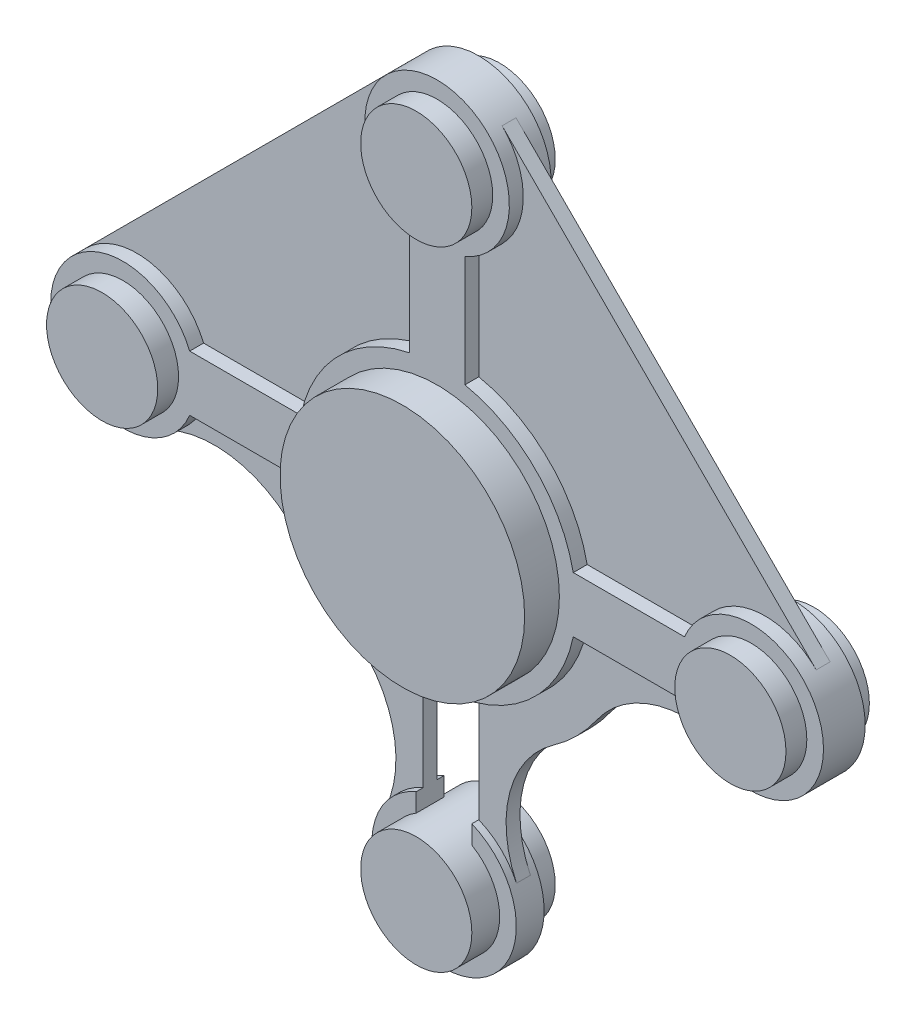
SolidWorks part; units mm, degrees
ref_plane "Front Plane" through (0, 0, 0) normal (0, 0, 1) x (1, 0, 0)
ref_plane "Top Plane" through (0, 0, 0) normal (0, 1, 0) x (1, 0, 0)
ref_plane "Right Plane" through (0, 0, 0) normal (1, 0, 0) x (0, 0, -1)
sketch "Sketch1" plane through (0, 0, 0) normal (0, 0, 1) x (1, 0, 0)
  line L0 (0, 0) -> (50000, 0) construction
  line L1 (0, 0) -> (0, 50000) construction
  line L2 (18.3848, 131.3848) -> (131.3848, 18.3848)
  line L3 (-18.3848, 131.3848) -> (-131.3848, 18.3848)
  line L4 (10, 89) -> (10, 63.2139)
  line L5 (-10, 89) -> (-10, 63.2139)
  line L6 (10, 63.2139) -> (10, 48.9898)
  line L7 (-10, 63.2139) -> (-10, 48.9898)
  line L8 (89, -10) -> (63.2139, -10)
  line L9 (63.2139, -10) -> (48.9898, -10)
  line L10 (89, 10) -> (63.2139, 10)
  line L11 (63.2139, 10) -> (48.9898, 10)
  line L12 (-10, -89) -> (-10, -63.2139)
  line L13 (-10, -63.2139) -> (-10, -48.9898)
  line L14 (10, -89) -> (10, -63.2139)
  line L15 (10, -63.2139) -> (10, -48.9898)
  line L16 (-89, 10) -> (-63.2139, 10)
  line L17 (-63.2139, 10) -> (-48.9898, 10)
  line L18 (-89, -10) -> (-63.2139, -10)
  line L19 (-63.2139, -10) -> (-48.9898, -10)
  line L20 (10, -89) -> (10, -95.6795)
  line L21 (-10, -89) -> (-10, -95.6795)
  circle A0 centre (0, 0) radius 44
  circle A1 centre (0, 0) radius 50
  circle A2 centre (113, 0) radius 20
  circle A3 centre (113, 0) radius 26
  circle A4 centre (0, 0) radius 113 construction
  circle A5 centre (0, 113) radius 20
  circle A6 centre (0, 113) radius 26
  circle A7 centre (-113, 0) radius 26
  circle A8 centre (-113, 0) radius 20
  circle A9 centre (0, -113) radius 26
  circle A10 centre (0, -113) radius 20
  arc A12 (102.0028, -23.5598) -> (52.3594, -36.8034) centre (85.0841, -59.8055) ccw
  arc A13 (23.5598, -102.0028) -> (36.8034, -52.3594) centre (59.8055, -85.0841) cw
  arc A14 (-23.5598, -102.0028) -> (-36.8034, -52.3594) centre (-59.8055, -85.0841) ccw
  arc A15 (-102.0028, -23.5598) -> (-52.3594, -36.8034) centre (-85.0841, -59.8055) cw
  arc A16 (-52.3594, -36.8034) -> (-36.8034, -52.3594) centre (0, 0) ccw
  arc A17 (36.8034, -52.3594) -> (52.3594, -36.8034) centre (0, 0) ccw
  point P64 (0, 0)
  dimension "D1" = 88
  dimension "D2" = 100
  dimension "D3" = 40
  dimension "D4" = 52
  dimension "D5" = 226
  dimension "D6" = 52
  dimension "D7" = 40
  dimension "D8" = 4
  dimension "D9" = 40
  dimension "D10" = 40
  dimension "D11" = 20
extrude "Boss-Extrude1" add sketch "Sketch1" along normal mid plane 30 contours A8 | A5 | A2 | A10 region at (0, -113, 0) region at (113, 0, 0) region at (0, 113, 0) region at (-113, 0, 0)
extrude "Boss-Extrude2" add sketch "Sketch1<3>" along normal mid plane 40 separate body contours A0 region at (0, 0, 0)
sketch "Sketch1<3>" plane through (0, 0, 0) normal (0, 0, 1) x (1, 0, 0) same geometry as "Sketch1"
extrude "Boss-Extrude3" add sketch "Sketch1<4>" along normal mid plane 5 separate body contours L3 A7 L16 L17 A1 L7 L5 A6 | A6 L4 L6 A1 L11 L10 A3 L2 | A13 A17 A12 A3 L8 L9 A1 L15 L14 A9 | A15 A16 A14 A9 L12 L13 A1 L19 L18 A7 region at (55.9029, 55.9029, 0) region at (-55.9029, 55.9029, 0) region at (41.5793, -41.5793, 0) region at (-41.5793, -41.5793, 0)
sketch "Sketch1<4>" plane through (0, 0, 0) normal (0, 0, 1) x (1, 0, 0) same geometry as "Sketch1"
extrude "Boss-Extrude5" add sketch "Sketch1<6>" along normal mid plane 10 contours L20 A10 L21 A9 region at (24.6784, -107.5239, 0)
sketch "Sketch1<6>" plane through (0, 0, 0) normal (0, 0, 1) x (1, 0, 0) same geometry as "Sketch1"
extrude "Boss-Extrude6" add sketch "Sketch1<7>" along normal mid plane 15 separate body contours A6 L5 L7 A1 L6 L4 | A6 A5 | A3 L10 L11 A1 L9 L8 | L16 A7 L18 L19 A1 L17 | A7 A8 | A1 A0 | A3 A2 region at (23.3415, 122.6683, 0) region at (136.3415, 9.6683, 0) region at (68.6638, 0, 0) region at (0, 68.6638, 0) region at (-108.097, 24.7843, 0) region at (-68.6638, 0, 0) region at (48.3398, 4.8833, 0)
sketch "Sketch1<7>" plane through (0, 0, 0) normal (0, 0, 1) x (1, 0, 0) same geometry as "Sketch1"
